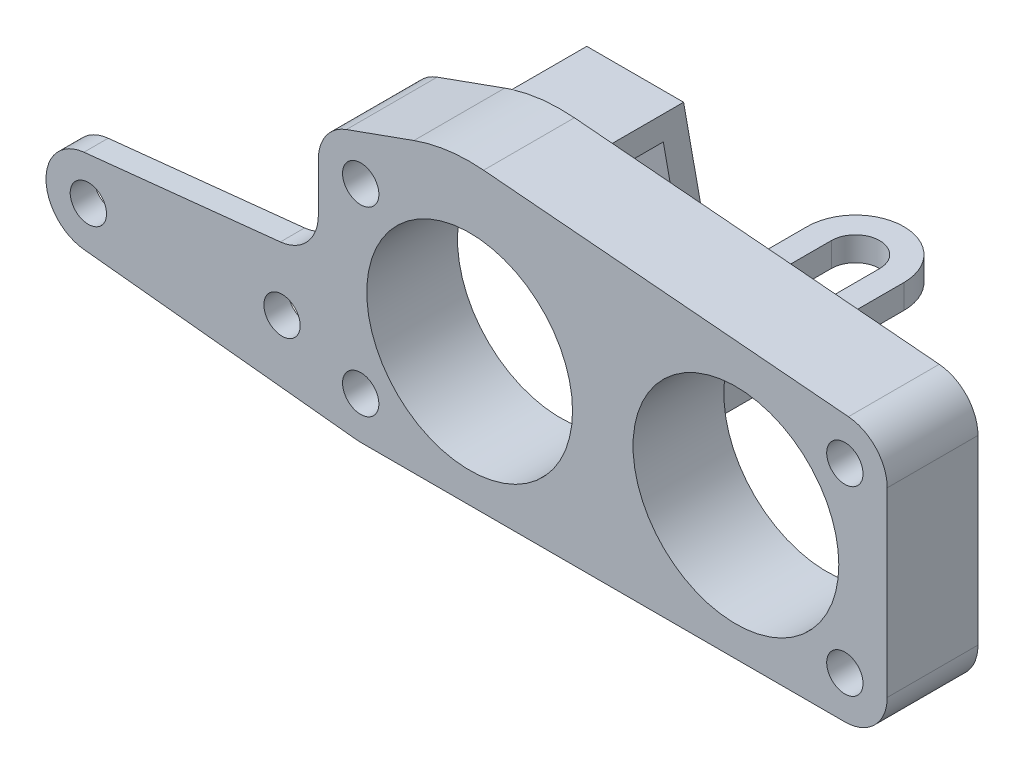
SolidWorks part; units mm, degrees
ref_plane "Front Plane" through (0, 0, 0) normal (0, 0, 1) x (1, 0, 0)
ref_plane "Top Plane" through (0, 0, 0) normal (0, 1, 0) x (1, 0, 0)
ref_plane "Right Plane" through (0, 0, 0) normal (1, 0, 0) x (0, 0, -1)
sketch "Sketch1" plane through (0, 0, 0) normal (0, 0, 1) x (1, 0, 0)
  line L0 (0, 0) -> (22, 0) construction
  line L3 (-12.5, -7.5) -> (-12.5, 7.5)
  line L4 (-9, 11) -> (31, 11)
  line L5 (34.5, 7.5) -> (34.5, -7.5)
  line L6 (31, -11) -> (-9, -11)
  line L7 (-9, 7.5) -> (-9, -7.5) construction
  line L8 (-9, -7.5) -> (31, -7.5) construction
  line L9 (31, -7.5) -> (31, 7.5) construction
  line L10 (31, 7.5) -> (-9, 7.5) construction
  line L11 (-9, 0) -> (0, 0) construction
  line L12 (11, 7.5) -> (11, 0) construction
  circle A0 centre (0, 0) radius 8.5
  circle A1 centre (22, 0) radius 8.5
  arc A4 (-12.5, 7.5) -> (-9, 11) centre (-9, 7.5) cw
  arc A5 (31, 11) -> (34.5, 7.5) centre (31, 7.5) cw
  arc A6 (34.5, -7.5) -> (31, -11) centre (31, -7.5) cw
  arc A7 (-9, -11) -> (-12.5, -7.5) centre (-9, -7.5) cw
  circle A8 centre (-9, 7.5) radius 1.5
  circle A9 centre (31, 7.5) radius 1.5
  circle A10 centre (31, -7.5) radius 1.5
  circle A11 centre (-9, -7.5) radius 1.5
  dimension "D1" = 17
  dimension "D5" = 3.5
  dimension "D6" = 3
  dimension "D2" = 22
  dimension "D3" = 22
  dimension "D4" = 47
extrude "Boss-Extrude1" add sketch "Sketch1" along normal blind 7.5
sketch "Sketch2" plane through (0, 0, 7.5) normal (0, 0, 1) x (1, 0, 0)
  line L0 (-31.5, -5.15) -> (-15.5, -5.15) construction
  line L1 (-15.6364, 0.0259) -> (-31.8636, -1.6689)
  line L2 (-31.8636, -8.6311) -> (-9.3636, -10.9811)
  line L3 (-31.8636, -1.6689) -> (-31.8636, -8.6311) construction
  line L4 (-12.5, 0.3535) -> (-15.6364, 0.0259) construction
  line L5 (-9, -11) -> (31, -11)
  line L6 (34.5, -7.5) -> (34.5, 7.5)
  line L7 (31, 11) -> (-9, 11)
  line L8 (-12.5, 7.5) -> (-12.5, -7.5)
  line L9 (-9, -11) -> (31, -11)
  line L10 (34.5, -7.5) -> (34.5, 7.5)
  line L11 (31, 11) -> (-9, 11)
  line L12 (-12.5, 7.5) -> (-12.5, -7.5)
  circle A0 centre (-15.5, -5.15) radius 1.5
  circle A1 centre (-31.5, -5.15) radius 1.5
  circle A2 centre (-9, -7.5) radius 1.5 construction
  circle A3 centre (31, -7.5) radius 1.5 construction
  circle A4 centre (31, 7.5) radius 1.5 construction
  circle A5 centre (22, 0) radius 8.5 construction
  circle A6 centre (0, 0) radius 8.5 construction
  arc A7 (-12.5, -7.5) -> (-9, -11) centre (-9, -7.5) ccw
  arc A8 (31, -11) -> (34.5, -7.5) centre (31, -7.5) ccw
  arc A9 (34.5, 7.5) -> (31, 11) centre (31, 7.5) ccw
  arc A10 (-9, 11) -> (-12.5, 7.5) centre (-9, 7.5) ccw
  arc A11 (-12.5, -7.5) -> (-9, -11) centre (-9, -7.5) ccw
  arc A12 (31, -11) -> (34.5, -7.5) centre (31, -7.5) ccw
  arc A13 (34.5, 7.5) -> (31, 11) centre (31, 7.5) ccw
  arc A14 (-9, 11) -> (-12.5, 7.5) centre (-9, 7.5) ccw
  circle A15 centre (-9, 7.5) radius 1.5 construction
  circle A16 centre (-9, -7.5) radius 1.5
  circle A17 centre (31, -7.5) radius 1.5
  circle A18 centre (31, 7.5) radius 1.5
  circle A19 centre (22, 0) radius 8.5
  circle A20 centre (0, 0) radius 8.5
  circle A21 centre (-9, 7.5) radius 1.5
  arc A22 (-31.8636, -1.6689) -> (-31.8636, -8.6311) centre (-31.5, -5.15) ccw
  arc A23 (-15.6364, 0.0259) -> (-12.5, 3.507) centre (-16, 3.507) ccw
  point P42 (0, 0)
  point P43 (0, 0)
  arc M16 (-12.5, -7.5) -> (-9, -11) centre (-9, -7.5) ccw
  arc M22 (-9, 11) -> (-12.5, 7.5) centre (-9, 7.5) ccw
  line M23 (-12.5, 7.5) -> (-12.5, -7.5)
  dimension "D1" = 2.35
  dimension "D5" = 3.5
  dimension "D2" = 6.5
  dimension "D3" = 16
  dimension "D4" = 0
extrude "Boss-Extrude2" add sketch "Sketch2" against normal blind 2 contours L1 A22 L2 A1 A0 M16 M23 M22 region at (-22.1761, -5.1359, 7.5)
sketch "Sketch3" plane through (0, 0, 0) normal (1, 0, 0) x (0, 0, -1)
  line L0 (-7.5, 11) -> (4.5, 11)
  line L1 (4.5, 11) -> (8.3792, -11)
  line L2 (8.3792, -11) -> (28.3792, -11)
  line L3 (-7.5, -11) -> (0, -11) construction
  line L4 (0, 7.5) -> (0, 11) construction
  dimension "D1" = 10
  dimension "D2" = 12
  dimension "D3" = 20
extrude "Extrude-Thin1" add sketch "Sketch3" along normal mid plane 8 thin thin type one direction reverse wall 2
sketch "Sketch4" plane through (0, 0, 7.5) normal (0, 0, 1) x (1, 0, 0)
  line L0 (-10.1835, 10.7938) -> (-4.5992, 12.8003)
  line L1 (1.1533, 13.5525) -> (31.2968, 10.9874)
  line L12 (-31.8636, -8.6311) -> (-9.3636, -10.9811)
  line L13 (-9, -11) -> (31, -11)
  line L14 (34.5, -7.5) -> (34.5, 7.5)
  line L15 (31, 11) -> (4, 11)
  line L16 (4, 11) -> (4, 13)
  line L17 (4, 13) -> (-4, 13)
  line L18 (-4, 13) -> (-4, 11)
  line L19 (-4, 11) -> (-9, 11)
  line L20 (-12.5, 7.5) -> (-12.5, 3.507)
  line L21 (-15.6364, 0.0259) -> (-31.8636, -1.6689)
  line L25 (31, 11) -> (4, 11)
  line L26 (4, 11) -> (4, 13)
  line L27 (4, 13) -> (-4, 13)
  line L28 (-4, 13) -> (-4, 11)
  line L29 (-4, 11) -> (-9, 11)
  arc A0 (-10.1835, 10.7938) -> (-12.5, 7.5) centre (-9, 7.5) ccw construction
  arc A1 (-4.5992, 12.8003) -> (1.1533, 13.5525) centre (0, 0) cw
  arc A2 (34.5, 7.5) -> (31, 11) centre (31, 7.5) ccw construction
  arc A3 (34.5, 7.5) -> (31.2968, 10.9874) centre (31, 7.5) ccw construction
  arc A4 (34.5, 7.5) -> (31.2968, 10.9874) centre (31, 7.5) ccw construction
  arc A10 (-9.3636, -10.9811) -> (-9, -11) centre (-9, -7.5) ccw
  arc A11 (31, -11) -> (34.5, -7.5) centre (31, -7.5) ccw
  arc A12 (34.5, 7.5) -> (31, 11) centre (31, 7.5) ccw
  arc A13 (-9, 11) -> (-12.5, 7.5) centre (-9, 7.5) ccw
  arc A14 (-15.6364, 0.0259) -> (-12.5, 3.507) centre (-16, 3.507) ccw
  arc A15 (-31.8636, -1.6689) -> (-31.8636, -8.6311) centre (-31.5, -5.15) ccw
  arc A18 (31.2968, 10.9874) -> (31, 11) centre (31, 7.5) ccw
  arc A19 (-9, 11) -> (-10.1835, 10.7938) centre (-9, 7.5) ccw
  point P0 (-10.8094, 10.496)
  arc M9 (34.5, 7.5) -> (31, 11) centre (31, 7.5) ccw
  line M10 (31, 11) -> (4, 11)
  line M11 (4, 11) -> (4, 13)
  line M12 (4, 13) -> (-4, 13)
  line M13 (-4, 13) -> (-4, 11)
  line M14 (-4, 11) -> (-9, 11)
  arc M15 (-9, 11) -> (-12.5, 7.5) centre (-9, 7.5) ccw
  dimension "D1" = 0
extrude "Boss-Extrude3" add sketch "Sketch4" against normal up to surface (7.5 mm away) contours A1 L0 M15 M14 M13 | A1 L1 M12 M11 M10 M9 region at (-5.8848, 11.6685, 7.5) region at (11.7624, 11.9186, 7.5) up to face at (32.5, -7.5, 0)
sketch "Sketch5" plane through (0, -9, 0) normal (0, 1, 0) x (1, 0, 0)
  line L0 (0, 24.3792) -> (0, 14.0574) construction
  line L1 (2, 24.3792) -> (2, 14.0574)
  line L2 (-2, 24.3792) -> (-2, 14.0574)
  line L3 (4, 10.0574) -> (-4, 10.0574) construction
  line L4 (4, 28.3792) -> (-4, 28.3792) construction
  arc A0 (2, 24.3792) -> (-2, 24.3792) centre (0, 24.3792) ccw
  arc A1 (-2, 14.0574) -> (2, 14.0574) centre (0, 14.0574) ccw
  point P3 (0, 19.2183)
  point P8 (0, 14.4686)
  dimension "D1" = 2
  dimension "D2" = 4
  dimension "D3" = 4
extrude "Cut-Extrude1" cut sketch "Sketch5" against normal blind 10
fillet "Fillet1" radius 4 2 edges at (-4, -10, -28.3792) (4, -10, -28.3792)
